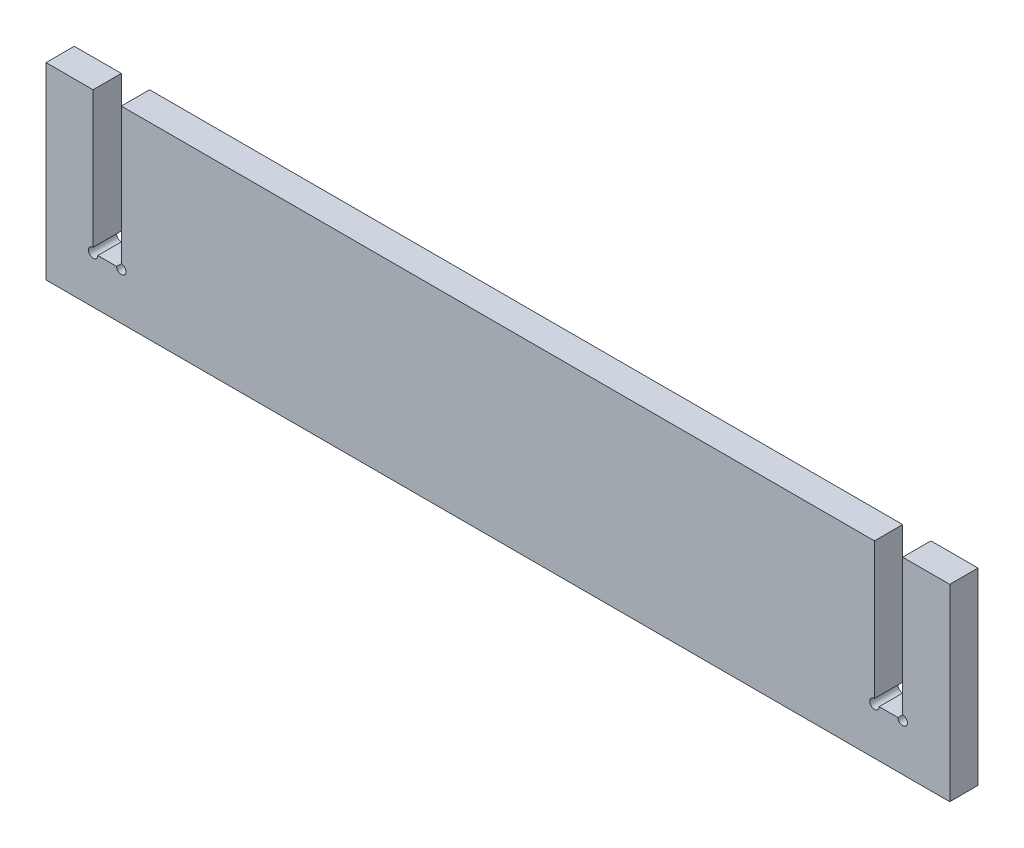
SolidWorks part; units mm, degrees
material "Acrylic (Medium-high impact)"
ref_plane "Front Plane" through (0, 0, 0) normal (0, 0, 1) x (1, 0, 0)
ref_plane "Top Plane" through (0, 0, 0) normal (0, 1, 0) x (1, 0, 0)
ref_plane "Right Plane" through (0, 0, 0) normal (1, 0, 0) x (0, 0, -1)
sketch "Sketch1" plane through (0, 0, 0) normal (0, 0, 1) x (1, 0, 0)
  line L0 (-43, 10) -> (-43, -5)
  line L1 (-48, -10) -> (48, -10)
  line L2 (-48, -10) -> (-48, 10)
  line L3 (-48, 10) -> (-43, 10)
  line L4 (48, -10) -> (48, 10)
  line L5 (-48, -10) -> (48, 10) construction
  line L6 (-48, 10) -> (48, -10) construction
  line L7 (-43, -5) -> (-40, -5)
  line L8 (-40, -5) -> (-40, 10)
  line L9 (40, 10) -> (40, -5)
  line L10 (40, -5) -> (43, -5)
  line L11 (43, -5) -> (43, 10)
  line L12 (43, 10) -> (48, 10)
  line L13 (-40, 10) -> (40, 10)
  point P0 (0, 0)
  dimension "D1" = 3
  dimension "D2" = 80
  dimension "D3" = 5
  dimension "D4" = 20
  dimension "D5" = 5
extrude "Boss-Extrude1" add sketch "Sketch1" along normal blind 3
sketch "Sketch2" plane through (0, 0, 3) normal (0, 0, 1) x (1, 0, 0)
  circle A0 centre (-43, -5) radius 0.5
  circle A1 centre (-40, -5) radius 0.5
  circle A2 centre (40, -5) radius 0.5
  circle A3 centre (43, -5) radius 0.5
  dimension "D1" = 1
extrude "Cut-Extrude1" cut sketch "Sketch2" against normal through all
